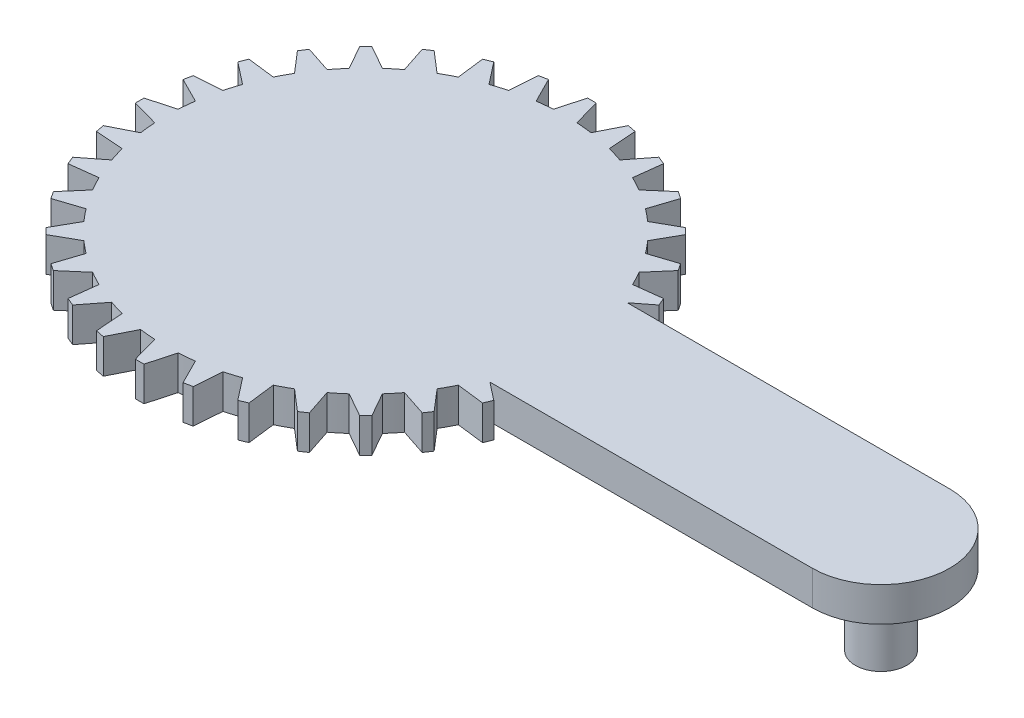
SolidWorks part; units mm, degrees
note: The reader was unsure of these and kept them because the rebuilt part matched: shared geometry of "Sketch4<3>", "Sketch4<5>".
ref_plane "Front Plane" through (0, 0, 0) normal (0, 0, 1) x (1, 0, 0)
ref_plane "Top Plane" through (0, 0, 0) normal (0, 1, 0) x (1, 0, 0)
ref_plane "Right Plane" through (0, 0, 0) normal (1, 0, 0) x (0, 0, -1)
sketch "Sketch3" plane through (0, 0, 0) normal (0, 1, 0) x (1, 0, 0)
  circle A0 centre (0, 0) radius 2.5
  dimension "D1" = 5
extrude "Boss-Extrude1" add sketch "Sketch3" along normal blind 4.15
sketch "Sketch4" plane through (0, 4.15, 0) normal (0, 1, 0) x (1, 0, 0)
  line L0 (0, 0) -> (30, 0) construction
  line L1 (30, 4) -> (10.9152, 4)
  line L2 (30, -4) -> (10.9152, -4)
  arc A7 (10.9152, 4) -> (10.9152, -4) centre (0, 0) ccw
  arc A8 (30, -4) -> (30, 4) centre (30, 0) ccw
  circle A9 centre (30, 0) radius 1.5
  point P1 (-0.2595, 0)
  dimension "D1" = 23.25
  dimension "D2" = 30
  dimension "D3" = 8
  dimension "D4" = 3
extrude "Boss-Extrude2" add sketch "Sketch4" along normal blind 2
extrude "Boss-Extrude3" add sketch "Sketch4<3>" along normal blind 2
sketch "Sketch4<3>" plane through (0, 4.15, 0) normal (0, 1, 0) x (1, 0, 0) same geometry as "Sketch4"
extrude "Boss-Extrude4" add sketch "Sketch4<5>" against normal up to surface (4.15 mm away) up to face at (0, 0, 2.5)
sketch "Sketch4<5>" plane through (0, 4.15, 0) normal (0, 1, 0) x (1, 0, 0) same geometry as "Sketch4"
sketch "Sketch7" plane through (0, 6.15, 0) normal (0, 1, 0) x (1, 0, 0)
  line L0 (0, 0) -> (-12.7663, 0) construction
  line L1 (-12.7663, 0) -> (-11.3663, 0) construction
  line L2 (-11.3663, 0.75) -> (-11.3663, -0.75)
  line L3 (-13.1663, -0.25) -> (-13.1663, 0.25)
  line L4 (-13.1663, 0.25) -> (-11.3663, 0.75)
  line L5 (-11.3663, -0.75) -> (-13.1663, -0.25)
  point P6 (-11.3663, 0)
  point P9 (-13.1663, 0)
  point P10 (-6.4807, 1.253)
  point P11 (0, 0)
  point P16 (-11.1723, 0)
  dimension "D1" = 1.4
  dimension "D2" = 1.8
  dimension "D3" = 0.5
  dimension "D4" = 1.5
extrude "Boss-Extrude5" add sketch "Sketch7" against normal up to surface (2 mm away) up to face at (30, 4.15, 1.5)
pattern_circular "CirPattern1" count 32 over 360 about axis through (0, 0, 0) along (0, 1, 0) of "Boss-Extrude5"
